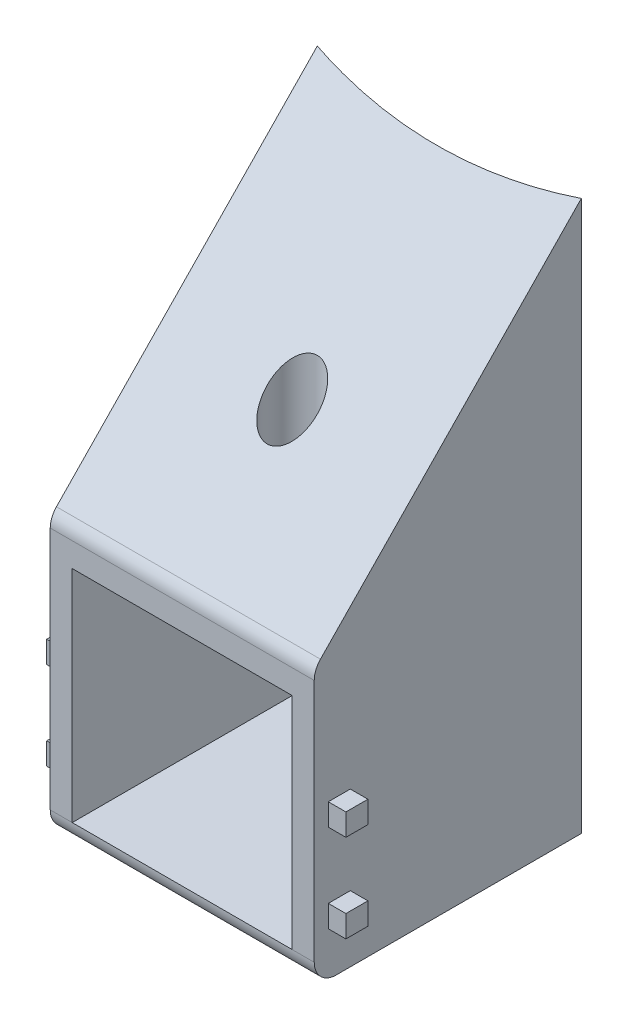
SolidWorks part; units mm, degrees
ref_plane "Front Plane" through (0, 0, 0) normal (0, 0, 1) x (1, 0, 0)
ref_plane "Top Plane" through (0, 0, 0) normal (0, 1, 0) x (1, 0, 0)
ref_plane "Right Plane" through (0, 0, 0) normal (1, 0, 0) x (0, 0, -1)
sketch "Sketch1" plane through (0, 0, 0) normal (0, 1, 0) x (1, 0, 0)
  line L0 (-15.24, 12.953) -> (15.24, 12.953)
  line L1 (-15.24, -16.51) -> (15.24, -16.51)
  line L2 (-15.24, -16.51) -> (-15.24, 16.51)
  line L3 (-15.24, 16.51) -> (15.24, 16.51)
  line L4 (15.24, -16.51) -> (15.24, 16.51)
  line L5 (-15.24, -16.51) -> (15.24, 16.51) construction
  line L6 (-15.24, 16.51) -> (15.24, -16.51) construction
  line L7 (-15.24, 12.953) -> (-15.24, 14.324)
  line L8 (15.24, 12.953) -> (15.24, 14.324)
  line L9 (-15.24, 14.324) -> (-15.24, 16.51)
  line L10 (-15.24, 16.51) -> (15.24, 16.51)
  circle A0 centre (0, 91.1867) radius 78.359
  point P0 (0, 0)
  dimension "D1" = 33.02
  dimension "D2" = 30.48
extrude "Boss-Extrude1" add sketch "Sketch1" along normal mid plane 63.5 contours A0 L0 L2 L1 L4 | A0 L2 L0 | A0 L0 L4 region at (-12.0463, 0, -13.375) region at (0, 0, 1.7906) region at (12.0463, 0, -13.375)
sketch "Sketch3" plane through (0, 0, 16.51) normal (0, 0, 1) x (1, 0, 0)
  line L0 (15.24, 31.75) -> (15.24, -31.75) construction
  line L1 (-12.7, -3.81) -> (12.7, -3.81)
  line L2 (-12.7, -3.81) -> (-12.7, -29.21)
  line L3 (-12.7, -29.21) -> (12.7, -29.21)
  line L4 (12.7, -3.81) -> (12.7, -29.21)
  line L5 (-12.7, -3.81) -> (12.7, -29.21) construction
  line L6 (-12.7, -29.21) -> (12.7, -3.81) construction
  line L7 (-15.24, -31.75) -> (15.24, -31.75) construction
  point P0 (0, -16.51)
  dimension "D1" = 2.54
  dimension "D2" = 25.4
  dimension "D3" = 25.4
  dimension "D4" = 2.54
extrude "Cut-Extrude1" cut sketch "Sketch3" against normal blind 25.4
sketch "Sketch4" plane through (15.24, 0, 0) normal (1, 0, 0) x (0, 0, -1)
  line L3 (-16.51, 31.75) -> (14.324, 31.75)
  line L4 (14.324, 31.75) -> (-16.51, 0)
  line L5 (-16.51, 31.75) -> (-16.51, -31.75) construction
  line L6 (-16.51, 0) -> (-16.51, 31.75)
extrude "Cut-Extrude2" cut sketch "Sketch4" against normal blind 30.48
sketch "Sketch5" plane through (15.24, 0, 0) normal (1, 0, 0) x (0, 0, -1)
  line L0 (-16.51, -31.75) -> (14.324, -31.75) construction
  line L1 (-14.886, -24.13) -> (-12.346, -24.13)
  line L2 (-14.886, -24.13) -> (-14.886, -26.67)
  line L3 (-14.886, -26.67) -> (-12.346, -26.67)
  line L4 (-12.346, -24.13) -> (-12.346, -26.67)
  line L5 (14.324, 31.75) -> (14.324, -31.75) construction
  line L11 (-12.346, -13.97) -> (-14.886, -13.97)
  line L12 (-12.346, -13.97) -> (-12.346, -16.51)
  line L13 (-12.346, -16.51) -> (-14.886, -16.51)
  line L14 (-14.886, -13.97) -> (-14.886, -16.51)
  dimension "D1" = 2.54
  dimension "D2" = 2.54
  dimension "D3" = 5.08
  dimension "D4" = 26.67
  dimension "D5" = 2.54
  dimension "D6" = 7.62
extrude "Boss-Extrude2" add sketch "Sketch5" along normal blind 2.032
sketch "Sketch7" plane through (-15.24, 0, 0) normal (-1, 0, 0) x (0, 0, 1)
  line L0 (16.51, -31.75) -> (-14.324, -31.75) construction
  line L1 (12.346, -24.13) -> (14.886, -24.13)
  line L2 (12.346, -24.13) -> (12.346, -26.67)
  line L3 (12.346, -26.67) -> (14.886, -26.67)
  line L4 (14.886, -24.13) -> (14.886, -26.67)
  line L5 (-14.324, 31.75) -> (-14.324, -31.75) construction
  line L7 (12.346, -13.97) -> (14.886, -13.97)
  line L8 (12.346, -13.97) -> (12.346, -16.51)
  line L9 (12.346, -16.51) -> (14.886, -16.51)
  line L10 (14.886, -13.97) -> (14.886, -16.51)
  point P12 (13.616, -13.97)
  dimension "D1" = 5.08
  dimension "D2" = 26.67
  dimension "D3" = 2.54
  dimension "D4" = 2.54
  dimension "D5" = 2.54
  dimension "D6" = 7.62
extrude "Boss-Extrude3" add sketch "Sketch7" along normal blind 2.032
sketch "Sketch18" plane through (0, -3.81, 0) normal (0, -1, 0) x (1, 0, 0)
  line L0 (-15.24, 16.51) -> (15.24, 16.51) construction
  point P0 (0, 3.81)
  dimension "D1" = 12.7
hole_wizard "#1 (0.228) Diameter Hole3" positions "Sketch20" profile "Sketch21" hole size "#1" standard "ANSI Inch" end condition through all
sketch "Sketch20" plane through (0, -3.81, 0) normal (0, -1, 0) x (-1, 0, 0)
  point P0 (0, -3.81)
sketch "Sketch21" plane through (0, -3.81, 3.81) normal (1, 0, 0) x (0, 0, -1)
  line L0 (0, 0) -> (0, 35.56)
  line L1 (0, 35.56) -> (2.8956, 35.56)
  line L2 (2.8956, 35.56) -> (2.8956, 0.1207)
  line L3 (2.8956, 0.1207) -> (3.0162, 0)
  line L5 (3.0162, 0) -> (0, 0)
  line L6 (-2.8956, 0.1207) -> (-3.0162, 0) construction
  line L11 (0, -6.35) -> (0, 107.95) construction
  dimension "Thru Hole Dia." = 5.7912
  dimension "Thru Hole Depth" = 35.56
  dimension "Near C'Sink Dia." = 6.0325
  dimension "Near C'Sink Angle" = 90
fillet "Fillet1" radius 2.54 1 edges at (0, 0, 16.51)
fillet "Fillet2" radius 2.54 1 edges at (0, -31.75, 16.51)
hole_wizard "Tap Drill for #6-32 Tap1" positions "Sketch22" profile "Sketch23" hole size "#6-32" standard "ANSI Inch" end condition through all
sketch "Sketch22" plane through (0, 0, -8.89) normal (0, 0, 1) x (1, 0, 0)
  point P0 (-8.6881, -16.8142)
sketch "Sketch23" plane through (-8.6881, -16.8142, -8.89) normal (1, 0, 0) x (0, -1, 0)
  line L0 (0, 0) -> (0, 5.434)
  line L1 (0, 5.434) -> (1.3525, 5.434)
  line L2 (1.3525, 5.434) -> (1.3525, 0.635)
  line L3 (1.3525, 0.635) -> (1.9875, 0)
  line L5 (1.9875, 0) -> (0, 0)
  line L6 (-1.3525, 0.635) -> (-1.9875, 0) construction
  line L11 (0, -6.35) -> (0, 107.95) construction
  dimension "Thru Hole Dia." = 2.7051
  dimension "Thru Hole Depth" = 5.434
  dimension "Near C'Sink Dia." = 3.9751
  dimension "Near C'Sink Angle" = 90
hole_wizard "Tap Drill for #6-32 Tap2" positions "Sketch24" profile "Sketch25" hole size "#6-32" standard "ANSI Inch" end condition through all
sketch "Sketch24" plane through (0, 0, -8.89) normal (0, 0, 1) x (1, 0, 0)
  point P0 (8.657, -16.6676)
sketch "Sketch25" plane through (8.657, -16.6676, -8.89) normal (1, 0, 0) x (0, -1, 0)
  line L0 (0, 0) -> (0, 5.434)
  line L1 (0, 5.434) -> (1.3525, 5.434)
  line L2 (1.3525, 5.434) -> (1.3525, 0.635)
  line L3 (1.3525, 0.635) -> (1.9875, 0)
  line L5 (1.9875, 0) -> (0, 0)
  line L6 (-1.3525, 0.635) -> (-1.9875, 0) construction
  line L11 (0, -6.35) -> (0, 107.95) construction
  dimension "Thru Hole Dia." = 2.7051
  dimension "Thru Hole Depth" = 5.434
  dimension "Near C'Sink Dia." = 3.9751
  dimension "Near C'Sink Angle" = 90
